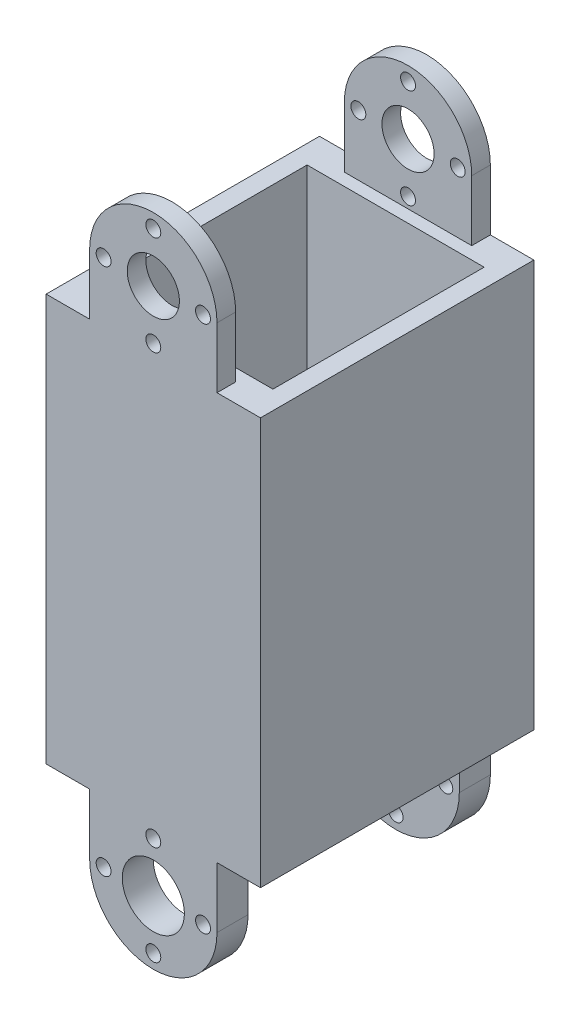
SolidWorks part; units mm, degrees
ref_plane "Front Plane" through (0, 0, 0) normal (0, 0, 1) x (1, 0, 0)
ref_plane "Top Plane" through (0, 0, 0) normal (0, 1, 0) x (1, 0, 0)
ref_plane "Right Plane" through (0, 0, 0) normal (1, 0, 0) x (0, 0, -1)
sketch "Sketch1" plane through (0, 0, 0) normal (0, 0, 1) x (1, 0, 0)
  line L0 (0, 0) -> (0, -100) construction
  line L1 (0, -100) -> (-70, -100) construction
  line L2 (-10.25, -60) -> (-70, -60) construction
  line L4 (-10.25, 0) -> (10.25, 0)
  line L5 (-10.25, 0) -> (-10.25, -60)
  line L7 (10.25, 0) -> (10.25, -60)
  line L8 (-10.25, 0) -> (10.25, 0)
  line L9 (-10.25, 0) -> (-10.25, -100)
  line L10 (-10.25, -100) -> (10.25, -100)
  line L11 (10.25, 0) -> (10.25, -100)
  circle A0 centre (0, 0) radius 10.25
  circle A1 centre (0, 0) radius 8
  circle A2 centre (0, 0) radius 4.2
  circle A3 centre (0, 8) radius 1.2
  circle A4 centre (8, 0) radius 1.2
  circle A5 centre (0, -8) radius 1.2
  circle A6 centre (-8, 0) radius 1.2
  point P16 (0, 0)
  dimension "D1" = 20.5
  dimension "D2" = 16
  dimension "D3" = 8.4
  dimension "D4" = 2.4
  dimension "D6" = 100
  dimension "D7" = 70
  dimension "D8" = 40
  dimension "D5" = 4
extrude "Boss-Extrude1" add sketch "Sketch1" along normal blind 22 and the other way blind 22 contours A0 L5 L7 | A6 L4 A0 A4 A1 A5 | A6 A1 A5 A4 L4 A2 | A6 L4 A2 A4 A1 A3 | A6 A1 A3 A4 L4 A0 region at (8.972, 1.0478, 0) region at (9.725, -0.2292, 0) region at (6.9906, -0.9364, 0) region at (5.5, 0.1769, 0) region at (0, -53.9967, 0)
sketch "Sketch2" plane through (-10.25, 0, 0) normal (-1, 0, 0) x (0, 0, 1)
  line L0 (22, 10.25) -> (-22, 10.25) construction
  line L1 (-19, 10.25) -> (19, 10.25)
  line L2 (-19, 10.25) -> (-19, -9.75)
  line L3 (-19, -9.75) -> (19, -9.75)
  line L4 (19, 10.25) -> (19, -9.75)
  line L5 (22, 0) -> (22, 10.25) construction
  line L6 (-22, 10.25) -> (-22, 0) construction
  dimension "D1" = 3
  dimension "D2" = 3
  dimension "D3" = 20
extrude "Cut-Extrude1" cut sketch "Sketch2" against normal through all
sketch "Sketch3" plane through (0, -9.75, 0) normal (0, 1, 0) x (1, 0, 0)
  line L1 (-10.25, 22) -> (-17.25, 22)
  line L2 (-10.25, 22) -> (-10.25, -22)
  line L3 (-10.25, -22) -> (-17.25, -22)
  line L4 (-17.25, 22) -> (-17.25, -22)
  line L5 (10.25, 22) -> (17.25, 22)
  line L6 (10.25, 22) -> (10.25, -22)
  line L7 (10.25, -22) -> (17.25, -22)
  line L8 (17.25, 22) -> (17.25, -22)
  dimension "D1" = 7
  dimension "D2" = 7
extrude "Boss-Extrude2" add sketch "Sketch3" against normal blind 65.5
sketch "Sketch23" plane through (0, 0, 22) normal (0, 0, 1) x (1, 0, 0)
  line L0 (10.25, -75.25) -> (17.25, -75.25) construction
  line L4 (10.25, -100) -> (-10.25, -100)
  line L5 (10.25, -100) -> (10.25, -75.25)
  line L6 (10.25, -75.25) -> (-10.25, -75.25)
  line L7 (-10.25, -100) -> (-10.25, -75.25)
  circle A0 centre (0, -85) radius 5
  circle A1 centre (0, 0) radius 4.2 construction
  circle A2 centre (0, -85) radius 8
  circle A3 centre (0, -77) radius 1.2
  circle A5 centre (8, -85) radius 1.2
  circle A6 centre (0, -93) radius 1.2
  circle A7 centre (-8, -85) radius 1.2
  circle A8 centre (0, -85) radius 10.25
  point P20 (0, -85)
  line M11 (-10.25, -100) -> (10.25, -100)
  line M12 (10.25, -100) -> (10.25, -75.25)
  dimension "D1" = 85
  dimension "D2" = 9.75
  dimension "D3" = 2.4
  dimension "D4" = 4
extrude "Cut-Extrude2" cut sketch "Sketch23" against normal through all contours A8 L7 M11 M12 | A2 A7 | A2 A7 | A2 A3 | A2 A3 | A2 A5 | A2 A5 | A2 A6 | A2 A6 | A0 region at (0, -96.1486, 22) region at (0, -85, 22) region at (7.4748, -85, 22) region at (8.4927, -85, 22) region at (0, -77.5252, 22) region at (0, -76.5073, 22) region at (0, -93.4927, 22) region at (0, -92.4748, 22) region at (-7.4748, -85, 22) region at (-8.4927, -85, 22)
sketch "Sketch24" plane through (0, -9.75, 0) normal (0, 1, 0) x (1, 0, 0)
  line L0 (17.25, -22) -> (17.25, 22) construction
  line L1 (-14.25, 17) -> (14.25, 17)
  line L2 (-14.25, 17) -> (-14.25, -17)
  line L3 (-14.25, -17) -> (14.25, -17)
  line L4 (14.25, 17) -> (14.25, -17)
  line L5 (-17.25, 22) -> (-17.25, -22) construction
  line L6 (10.25, 19) -> (-10.25, 19) construction
  line L7 (10.25, -19) -> (-10.25, -19) construction
  dimension "D1" = 3
  dimension "D2" = 3
  dimension "D3" = 2
  dimension "D4" = 2
extrude "Cut-Extrude3" cut sketch "Sketch24" against normal through all
sketch "Sketch25" plane through (-17.25, 0, 0) normal (-1, 0, 0) x (0, 0, 1)
  line L0 (-22, -9.75) -> (22, -9.75) construction
  line L2 (22, -75.25) -> (22, -9.75) construction
  circle A0 centre (0, -42.5) radius 5
  dimension "D1" = 32.75
  dimension "D2" = 22
extrude "Cut-Extrude5" cut sketch "Sketch25" against normal blind 10
